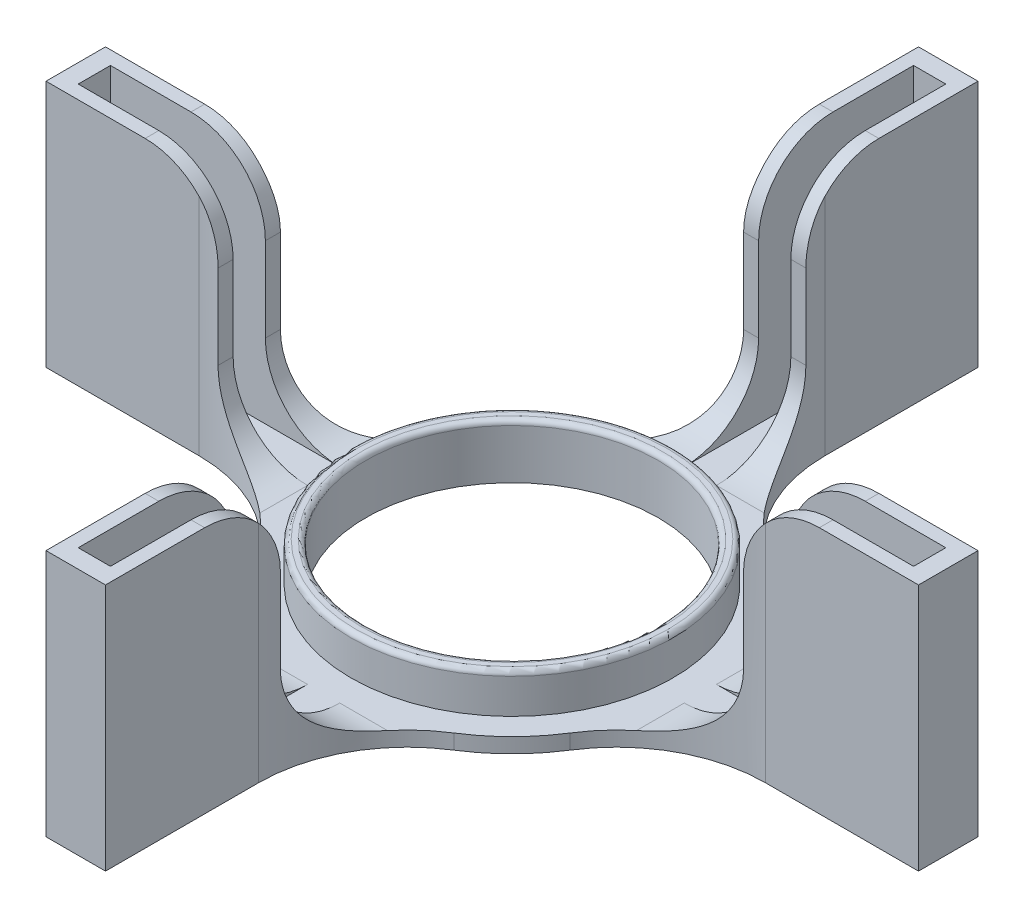
SolidWorks part; units mm, degrees
ref_plane "Front Plane" through (0, 0, 0) normal (0, 0, 1) x (1, 0, 0)
ref_plane "Top Plane" through (0, 0, 0) normal (0, 1, 0) x (1, 0, 0)
ref_plane "Right Plane" through (0, 0, 0) normal (1, 0, 0) x (0, 0, -1)
ref_plane "BASE THICKNESS" through (0, 3, 0) normal (0, 1, 0) x (1, 0, 0)
ref_plane "FIN HOLDER CRADDLE THICKNESS" through (0, 50, 0) normal (0, 1, 0) x (1, 0, 0)
ref_plane "TUBE ALIGNMENT INSERT" through (0, 11, 0) normal (0, 1, 0) x (1, 0, 0)
ref_axis "Axis1" through (0, 56.5, 0) along (0, -1, 0)
sketch "Sketch1" plane through (0, 0, 0) normal (0, 1, 0) x (1, 0, 0)
  circle A0 centre (0, 0) radius 37.5
  dimension "D1" = 75
extrude "BASE" add sketch "Sketch1" along normal up to surface (3 mm away) up to plane "BASE THICKNESS"
sketch "Sketch2" plane through (0, 0, 0) normal (0, 1, 0) x (1, 0, 0)
  line L1 (-6, 88) -> (6, 88)
  line L2 (-6, 88) -> (-6, 0)
  line L3 (-6, 0) -> (6, 0)
  line L4 (6, 88) -> (6, 0)
  dimension "D1" = 12
  dimension "D2" = 88
extrude "FIN EXTENSION BASE" add sketch "Sketch2" along normal up to surface (3 mm away) up to plane "BASE THICKNESS"
sketch "Sketch3" plane through (0, 0, 0) normal (0, 1, 0) x (1, 0, 0)
  line L0 (-6, 53) -> (-3.25, 53)
  line L1 (-3.25, 53) -> (-3.25, 84.25)
  line L2 (-3.25, 84.25) -> (3.25, 84.25)
  line L3 (3.25, 84.25) -> (3.25, 53)
  line L4 (3.25, 53) -> (6, 53)
  line L5 (6, 53) -> (6, 88)
  line L6 (6, 88) -> (-6, 88)
  line L7 (-6, 88) -> (-6, 53)
  dimension "D1" = 6.5
  dimension "D2" = 84.25
  dimension "D3" = 35
extrude "FIN CRADDLE" add sketch "Sketch3" along normal up to surface (50 mm away) up to plane "FIN HOLDER CRADDLE THICKNESS"
fillet "Fillet2" radius 30 2 edges at (6, 1.5, -37.0169) (-6, 1.5, -37.0169)
fillet "Fillet1" radius 15 4 edges at (-4.7656, 50, -53) (4.7656, 50, -53) (-4.7656, 3, -53) (4.7656, 3, -53)
pattern_circular "CirPattern1" count 4 over 360 about axis through (0, 56.5, 0) along (0, -1, 0) of "FIN EXTENSION BASE", "FIN CRADDLE", "Fillet2", "Fillet1"
sketch "Sketch4" plane through (0, 11, 0) normal (0, 1, 0) x (1, 0, 0)
  circle A0 centre (0, 0) radius 32.5
  circle A1 centre (0, 0) radius 29.5
  dimension "D1" = 65
  dimension "D2" = 3
extrude "Boss-Extrude5" add sketch "Sketch4" against normal up to surface (8 mm away) up to plane "BASE THICKNESS"
fillet "Fillet3" radius 5 1 edges at (0, 3, 29.5)
fillet "Fillet4" radius 1 2 edges at (0, 11, 29.5) (0, 11, 32.5)
sketch "Sketch5" plane through (0, 0, 0) normal (0, 1, 0) x (1, 0, 0)
  circle A2 centre (0, 0) radius 29.5 construction
  circle A3 centre (0, 0) radius 29.5
extrude "Cut-Extrude1" cut sketch "Sketch5" along normal through all
